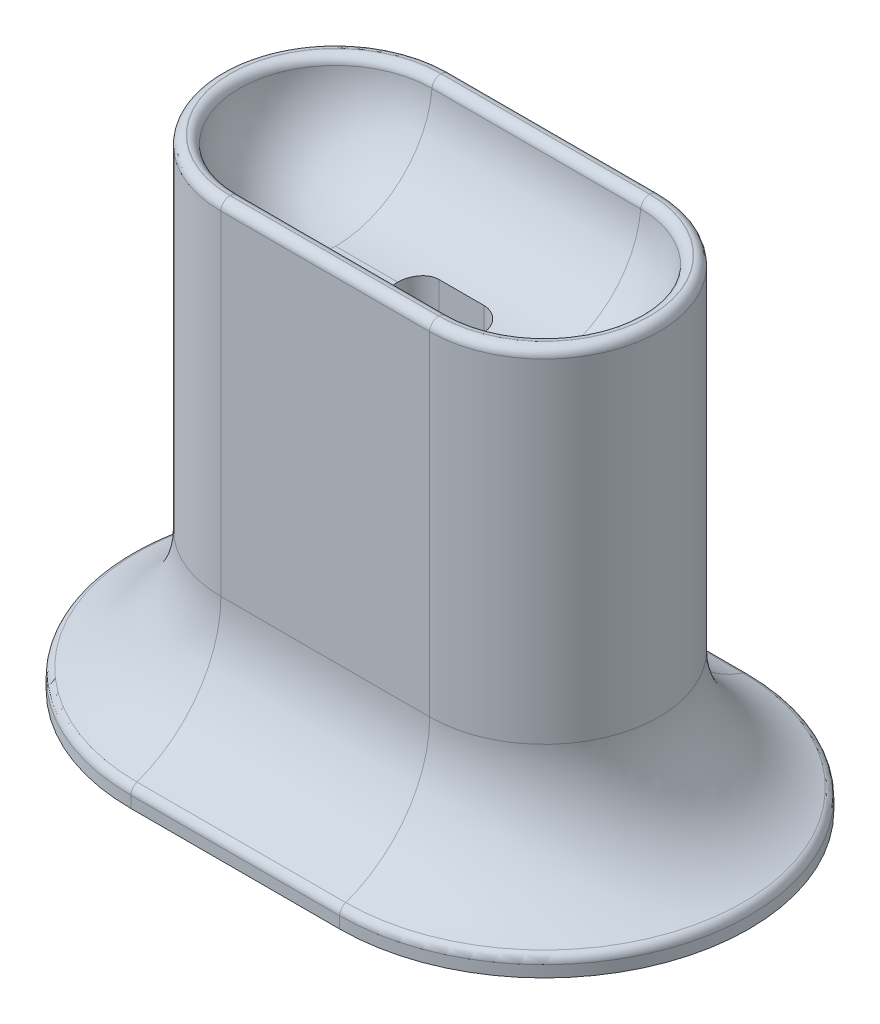
SolidWorks part; units mm, degrees
ref_plane "Front Plane" through (0, 0, 0) normal (0, 0, 1) x (1, 0, 0)
ref_plane "Top Plane" through (0, 0, 0) normal (0, 1, 0) x (1, 0, 0)
ref_plane "Right Plane" through (0, 0, 0) normal (1, 0, 0) x (0, 0, -1)
sketch "Sketch2" plane through (0, 0, 0) normal (0, 1, 0) x (1, 0, 0)
  line L0 (0, 10.75) -> (23.2, 10.75)
  line L1 (0, -10.75) -> (23.2, -10.75)
  line L2 (0, -12.75) -> (23.2, -12.75)
  line L3 (0, 12.75) -> (23.2, 12.75)
  line L4 (0, 22.75) -> (23.2, 22.75)
  line L5 (0, -22.75) -> (23.2, -22.75)
  arc A0 (0, 10.75) -> (0, -10.75) centre (0, 0) ccw
  arc A1 (23.2, -10.75) -> (23.2, 10.75) centre (23.2, 0) ccw
  arc A2 (0, 12.75) -> (0, -12.75) centre (0, 0) ccw
  arc A3 (23.2, -12.75) -> (23.2, 12.75) centre (23.2, 0) ccw
  arc A4 (23.2, -22.75) -> (23.2, 22.75) centre (23.2, 0) ccw
  arc A5 (0, 22.75) -> (0, -22.75) centre (0, 0) ccw
  dimension "D1" = 21.5
  dimension "D2" = 23.2
  dimension "D3" = 2
  dimension "D4" = 10
extrude "Boss-Extrude1" add sketch "Sketch2" along normal blind 53.5 contours L2 A3 L3 A2 A1 L1 A0 L0 region at (-12.2003, 0, 0)
extrude "Boss-Extrude2" add sketch "Sketch2<3>" against normal blind 10 from offset 42.75 contours L1 A1 L0 A0 region at (11.6, 0, 0)
sketch "Sketch2<3>" plane through (0, 0, 0) normal (0, 1, 0) x (1, 0, 0) same geometry as "Sketch2"
extrude "Boss-Extrude3" add sketch "Sketch2<4>" along normal blind 2 contours L4 A5 L5 A4 A3 L2 A2 L3 region at (11.6, 0, -21.926)
sketch "Sketch2<4>" plane through (0, 0, 0) normal (0, 1, 0) x (1, 0, 0) same geometry as "Sketch2"
fillet "Fillet1" radius 10.75 4 edges at (11.6, 42.75, -10.75) (33.95, 42.75, 0) (11.6, 42.75, 10.75) (-10.75, 42.75, 0)
fillet "Fillet2" radius 14 4 edges at (-12.75, 2, 0) (11.6, 2, -12.75) (35.95, 2, 0) (11.6, 2, 12.75)
fillet "Fillet3" radius 1 12 edges at (-22.75, 2, 0) (11.6, 2, 22.75) (45.95, 2, 0) (-10.75, 53.5, 0) (11.6, 53.5, 10.75) (33.95, 53.5, 0) (-12.75, 53.5, 0) (11.6, 53.5, 12.75) (35.95, 53.5, 0) (11.6, 2, -22.75) (11.6, 53.5, -10.75) (11.6, 53.5, -12.75)
sketch "Sketch3" plane through (0, 32.75, 0) normal (0, -1, 0) x (1, 0, 0)
  line L0 (9.2, 2.3) -> (14.2, 2.3)
  line L1 (9.2, -2.3) -> (14.2, -2.3)
  arc A0 (9.2, 2.3) -> (9.2, -2.3) centre (9.2, 0) ccw
  arc A1 (14.2, -2.3) -> (14.2, 2.3) centre (14.2, 0) ccw
  arc A2 (23.2, -10.75) -> (23.2, 10.75) centre (23.2, 0) ccw construction
  point P1 (16.5, 0)
  point P10 (33.95, 0)
  dimension "D1" = 4.6
  dimension "D2" = 5
  dimension "D3" = 17.45
sketch "Sketch4" plane through (0, 0, -10.75) normal (0, 0, 1) x (1, 0, 0)
  line L8 (13.6, 0) -> (9.6, 0)
  line L11 (13.6, 0) -> (13.6, 1.3313)
  line L12 (0, 0) -> (23.2, 0) construction
  line L13 (9.6, 0) -> (9.6, 1.3313)
  arc A2 (13.6, 1.3313) -> (9.6, 1.3313) centre (11.6, 2.8313) ccw
  point P10 (11.6, 2.8313)
  dimension "D1" = 5
  dimension "D2" = 4
  dimension "D3" = 34.35
  dimension "D4" = 2
extrude "Cut-Extrude4" cut sketch "Sketch4" against normal through all
extrude "Cut-Extrude5" cut sketch "Sketch3" against normal through all both and the other way through all
